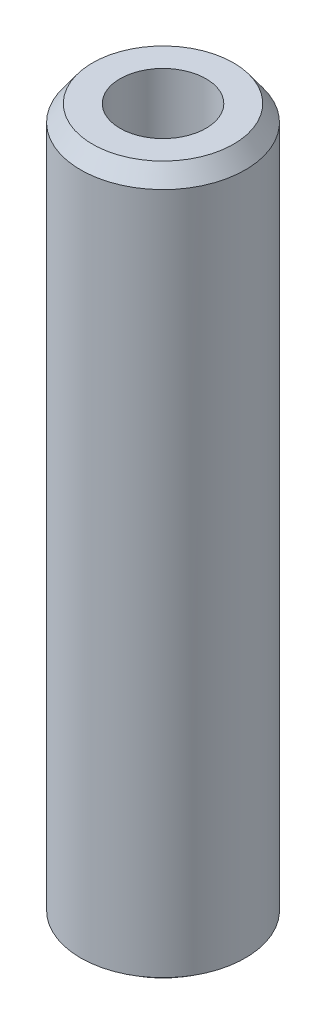
SolidWorks part; units mm, degrees
ref_plane "Front Plane" through (0, 0, 0) normal (0, 0, 1) x (1, 0, 0)
ref_plane "Top Plane" through (0, 0, 0) normal (0, 1, 0) x (1, 0, 0)
ref_plane "Right Plane" through (0, 0, 0) normal (1, 0, 0) x (0, 0, -1)
sketch "Sketch1" plane through (0, 0, 0) normal (0, 1, 0) x (1, 0, 0)
  circle A0 centre (0, 0) radius 15
  dimension "SHAFT_OD" = 30
extrude "Boss-Extrude1" add sketch "Sketch1" along normal blind 129.4232
sketch "Sketch2" plane through (0, 0, 0) normal (0, 1, 0) x (1, 0, 0)
  circle A0 centre (0, 0) radius 7.8304
  dimension "BORE_D" = 15.6608
extrude "Cut-Extrude1" cut sketch "Sketch2" along normal through all
chamfer "Chamfer1" distance 2.9737 angle 35.945 2 edges at (0, 129.4232, 15) (0, 0, 15) first distance on face at (0, 129.4232, 15) first distance on face at (0, 0, 7.8304)
